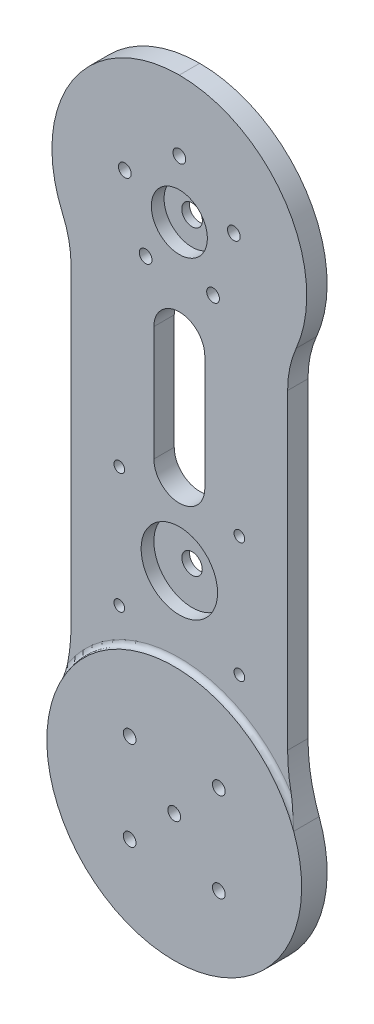
SolidWorks part; units mm, degrees
material "6061-O (SS)"
ref_plane "Ebene vorne" through (0, 0, 0) normal (0, 0, 1) x (1, 0, 0)
ref_plane "Ebene oben" through (0, 0, 0) normal (0, 1, 0) x (1, 0, 0)
ref_plane "Ebene rechts" through (0, 0, 0) normal (1, 0, 0) x (0, 0, -1)
sketch "Skizze1" plane through (0, 0, 0) normal (0, 0, 1) x (1, 0, 0)
  line L0 (0, 0) -> (0, 50000) construction
  line L1 (-50, 250) -> (50, 250)
  line L2 (-50, 250) -> (-50, -50)
  line L3 (-50, -50) -> (50, -50)
  line L4 (50, 250) -> (50, -50)
  line L5 (-50, 250) -> (50, -50) construction
  line L6 (-50, -50) -> (50, 250) construction
  point P0 (0, 100)
  point P8 (0, -50)
  dimension "D1" = 100
  dimension "D2" = 300
  dimension "D3" = 50
extrude "Aufsatz-Linear austragen1" add sketch "Skizze1" along normal blind 10
fillet "Verrundung1" radius 50 4 edges at (50, -50, 5) (-50, -50, 5) (-50, 250, 5) (50, 250, 5)
sketch "RiemenSchema" plane through (0, 0, 10) normal (0, 0, 1) x (1, 0, 0)
  line L0 (-37.0077, 193.2123) -> (-15.0932, 73.7317)
  line L1 (37.0077, 193.2123) -> (15.0932, 73.7317)
  line L3 (-28.5, 48) -> (28.5, 48) construction
  line L4 (-28.5, 48) -> (-28.5, 105) construction
  line L5 (-28.5, 105) -> (28.5, 105) construction
  line L6 (28.5, 48) -> (28.5, 105) construction
  line L7 (-28.5, 48) -> (28.5, 105) construction
  line L8 (-28.5, 105) -> (28.5, 48) construction
  circle A0 centre (0, 0) radius 76.5 construction
  circle A1 centre (0, 200) radius 50 construction
  circle A2 centre (0, 200) radius 37.625
  circle A3 centre (0, 76.5) radius 15.345
  dimension "D1" = 153
  dimension "D2" = 75.25
  dimension "D3" = 30.69
  dimension "D4" = 57
  dimension "D5" = 57
hole_wizard "Ø5.0 (5) Durchmesser Bohrung1" positions "Skizze3" profile "Skizze4" hole size "Ø5.0" standard "ISO" end condition through all
sketch "Skizze3" plane through (0, 0, 10) normal (0, 0, 1) x (1, 0, 0)
  line L1 (-17.5, -17.5) -> (17.5, -17.5)
  line L2 (-17.5, -17.5) -> (-17.5, 17.5)
  line L3 (-17.5, 17.5) -> (17.5, 17.5)
  line L4 (17.5, -17.5) -> (17.5, 17.5)
  line L5 (-17.5, -17.5) -> (17.5, 17.5) construction
  line L6 (-17.5, 17.5) -> (17.5, -17.5) construction
  point P1 (0, 0)
  point P2 (17.5, 17.5)
  point P37 (-17.5, -17.5)
  point P38 (-17.5, 17.5)
  point P39 (17.5, -17.5)
  point P51 (121.9963, 109.0985)
  dimension "D1" = 35
  dimension "D2" = 35
sketch "Skizze4" plane through (0, 0, 10) normal (1, 0, 0) x (0, -1, 0)
  line L0 (0, 0) -> (0, 10)
  line L1 (0, 10) -> (2.5, 10)
  line L2 (2.5, 10) -> (2.5, 0)
  line L5 (2.5, 0) -> (0, 0)
  line L11 (0, -6.35) -> (0, 107.95) construction
  dimension "Bohrerdurchmesser" = 5
  dimension "Bohrungstiefe" = 10
sketch "Skizze27" plane through (0, 0, 10) normal (0, 0, 1) x (1, 0, 0)
  line L0 (-67.9504, 100) -> (75.5745, 100) construction
  line L1 (0, 0) -> (0, 167.6934) construction
  circle A0 centre (0, 81.5) radius 15
  dimension "D2" = 30
  dimension "D1" = 100
  dimension "D3" = 18.5
extrude "Schnitt-Linear austragen8" cut sketch "Skizze27" against normal blind 7
sketch "Skizze28" plane through (0, 0, 3) normal (0, 0, 1) x (1, 0, 0)
  circle A0 centre (0, 81.5) radius 4
  dimension "D1" = 8
extrude "Schnitt-Linear austragen9" cut sketch "Skizze28" against normal through all
hole_wizard "M5 Gewindebohrung1" positions "Skizze31" profile "Skizze32" tap size "M5" standard "ISO" end condition through all
sketch "Skizze31" plane through (0, 0, 10) normal (0, 0, 1) x (1, 0, 0)
  line L1 (-23.57, 57.93) -> (23.57, 57.93) construction
  line L2 (-23.57, 57.93) -> (-23.57, 105.07) construction
  line L3 (-23.57, 105.07) -> (23.57, 105.07) construction
  line L4 (23.57, 57.93) -> (23.57, 105.07) construction
  line L5 (-23.57, 57.93) -> (23.57, 105.07) construction
  line L6 (-23.57, 105.07) -> (23.57, 57.93) construction
  point P1 (0, 81.5)
  point P2 (23.57, 105.07)
  point P47 (-23.57, 57.93)
  point P48 (-23.57, 105.07)
  point P49 (23.57, 57.93)
  dimension "D1" = 47.14
  dimension "D2" = 47.14
sketch "Skizze32" plane through (0, 81.5, 10) normal (1, 0, 0) x (0, -1, 0)
  line L0 (0, 0) -> (0, 10)
  line L1 (0, 10) -> (2.1, 10)
  line L2 (2.1, 10) -> (2.1, 0)
  line L5 (2.1, 0) -> (0, 0)
  line L11 (0, -6.35) -> (0, 107.95) construction
  dimension "Bohrerdurchmesser" = 4.2
  dimension "Bohrungstiefe" = 10
hole_wizard "Ø8.1 (8.1) Durchmesser Bohrung1" positions "Skizze15" profile "Skizze16" hole size "Ø8.1" standard "ISO" end condition through all
sketch "Skizze15" plane through (0, 0, 10) normal (0, 0, 1) x (1, 0, 0)
  point P0 (0, 200)
sketch "Skizze16" plane through (0, 200, 10) normal (1, 0, 0) x (0, -1, 0)
  line L0 (0, 0) -> (0, 10)
  line L1 (0, 10) -> (4.05, 10)
  line L2 (4.05, 10) -> (4.05, 0)
  line L5 (4.05, 0) -> (0, 0)
  line L11 (0, -6.35) -> (0, 107.95) construction
  dimension "Bohrerdurchmesser" = 8.1
  dimension "Bohrungstiefe" = 10
sketch "Skizze17" plane through (0, 0, 10) normal (0, 0, 1) x (1, 0, 0)
  circle A0 centre (0, 200) radius 11
  dimension "D1" = 22
extrude "Schnitt-Linear austragen2" cut sketch "Skizze17" against normal blind 7
hole_wizard "Ø5.0 (5) Durchmesser Bohrung2" positions "Skizze18" profile "Skizze19" hole size "Ø5.0" standard "ISO" end condition through all
sketch "Skizze18" plane through (0, 0, 10) normal (0, 0, 1) x (1, 0, 0)
  line L0 (0, 0) -> (0, -50000) construction
  circle A0 centre (0, 200) radius 22.5 construction
  point P9 (0, 222.5)
  point P22 (21.3988, 206.9529)
  point P23 (13.2252, 181.7971)
  point P24 (-13.2252, 181.7971)
  point P25 (-21.3988, 206.9529)
  dimension "D1" = 45
  dimension "D2" = 5
sketch "Skizze19" plane through (-21.3988, 206.9529, 10) normal (1, 0, 0) x (0, -1, 0)
  line L0 (0, 0) -> (0, 10)
  line L1 (0, 10) -> (2.5, 10)
  line L2 (2.5, 10) -> (2.5, 0)
  line L5 (2.5, 0) -> (0, 0)
  line L11 (0, -6.35) -> (0, 107.95) construction
  dimension "Bohrerdurchmesser" = 5
  dimension "Bohrungstiefe" = 10
sketch "Skizze21" plane through (0, 0, 0) normal (0, 0, -1) x (-1, 0, 0)
  line L0 (0, 0) -> (0, -50000) construction
  line L1 (-50, 0) -> (-50, 200) construction
  line L2 (-42.5, 26.3391) -> (-42.5, 173.6609)
  line L3 (-50, 0) -> (-50, 200)
  arc A1 (-50, 200) -> (-42.5, 173.6609) centre (0, 200) ccw
  arc A2 (-42.5, 26.3391) -> (-50, 0) centre (0, 0) ccw
  arc A3 (0, 250) -> (-50, 200) centre (0, 200) ccw construction
  arc A4 (-50, 0) -> (0, -50) centre (0, 0) ccw construction
  dimension "D2" = 85
extrude "Schnitt-Linear austragen4" cut sketch "Skizze21" against normal blind 10
mirror "Spiegeln1" about plane through (0, 0, 0) normal (1, 0, 0) of "Schnitt-Linear austragen4"
fillet "Verrundung2" radius 40 2 edges at (-42.5, 173.6609, 5) (42.5, 173.6609, 5)
fillet "Verrundung3" radius 70 2 edges at (-42.5, 26.3391, 5) (42.5, 26.3391, 5)
sketch "Skizze22" plane through (0, 0, 0) normal (0, 0, -1) x (-1, 0, 0)
  line L0 (0, 0) -> (0, -50000) construction
  line L1 (0, 114.5) -> (0, 159.5) construction
  line L2 (-10, 114.5) -> (-10, 159.5)
  line L3 (10, 114.5) -> (10, 159.5)
  arc A0 (-10, 114.5) -> (10, 114.5) centre (0, 114.5) ccw
  arc A1 (10, 159.5) -> (-10, 159.5) centre (0, 159.5) ccw
  point P5 (0, 137)
  dimension "D1" = 20
  dimension "D2" = 45
  dimension "D3" = 137
extrude "Schnitt-Linear austragen5" cut sketch "Skizze22" against normal blind 10
sketch "Skizze26" plane through (0, 0, 10) normal (0, 0, -1) x (-1, 0, 0)
  line L0 (47.3677, 16.0093) -> (99.8813, 16.0093)
  line L1 (-92.2615, 257.1661) -> (99.8813, 257.1661)
  line L2 (-92.2615, 257.1661) -> (-92.2615, 16.0093)
  line L3 (-92.2615, 16.0093) -> (-47.3677, 16.0093)
  line L4 (99.8813, 257.1661) -> (99.8813, 16.0093)
  arc A0 (47.3677, 16.0093) -> (-47.3677, 16.0093) centre (0, 0) ccw
extrude "Schnitt-Linear austragen7" cut sketch "Skizze26" along normal blind 2
fillet "Verrundung5" radius 2 1 edges at (0, 50, 8)
